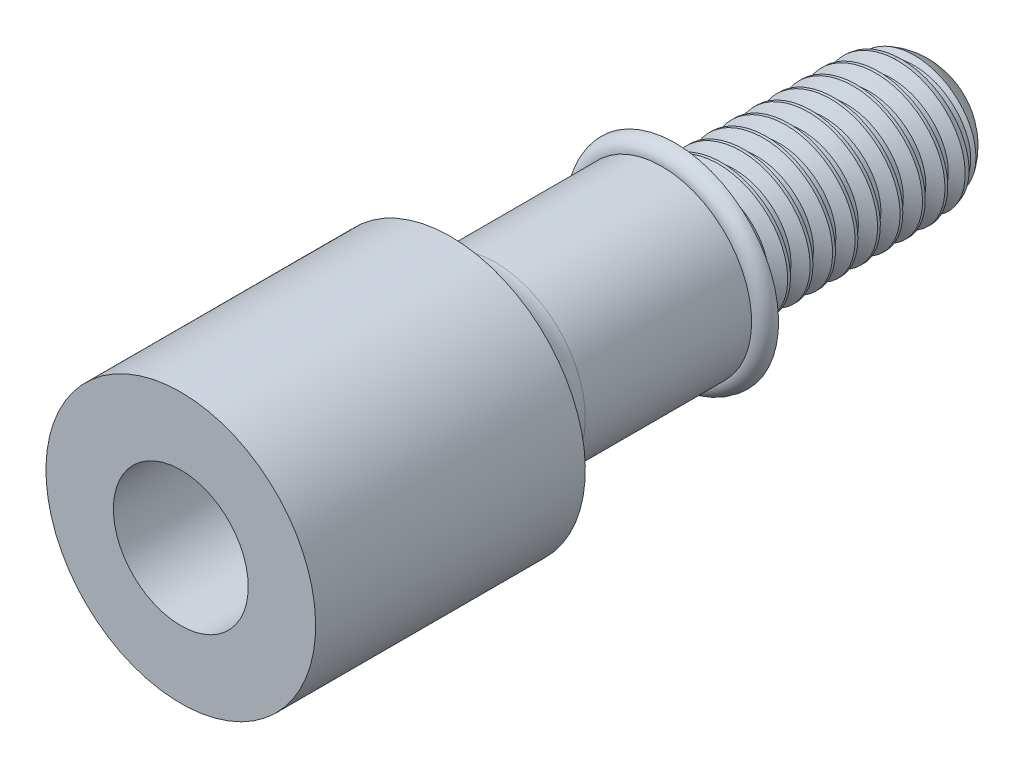
SolidWorks part; units mm, degrees
ref_plane "Front Plane" through (0, 0, 0) normal (0, 0, 1) x (1, 0, 0)
ref_plane "Top Plane" through (0, 0, 0) normal (0, 1, 0) x (1, 0, 0)
ref_plane "Right Plane" through (0, 0, 0) normal (1, 0, 0) x (0, 0, -1)
sketch "Sketch1" plane through (0, 0, 0) normal (1, 0, 0) x (0, 0, -1)
  line L0 (0, 0) -> (-11, 0)
  line L1 (-11, 0) -> (-11, 3)
  line L2 (-11, 3) -> (-5, 3)
  line L3 (-4, 2) -> (-0.3, 2)
  line L4 (0, 2.3) -> (0, 0)
  arc A0 (-5, 3) -> (-4, 2) centre (-4, 3) ccw
  arc A1 (-0.3, 2) -> (0, 2.3) centre (0, 2) cw
  dimension "D1" = 3
  dimension "D2" = 6
  dimension "D3" = 11
  dimension "D4" = 2
  dimension "D5" = 2.3
revolve "Revolve1" add sketch "Sketch1" angle 360 about L0
sketch "Sketch2" plane through (0, 0, 0) normal (0, 0, -1) x (-1, 0, 0)
  circle A0 centre (0, 0) radius 1.5
  dimension "D1" = 3
extrude "Boss-Extrude1" add sketch "Sketch2" along normal blind 6
fillet "Fillet1" radius 1.3 1 edges at (0, 1.5, -6)
thread "Thread1" pitch 0.5 method cut profile "Thread Profile1" start angle 0, offset 0, length 0, pitch 0.5, diameter 3
ref_plane "Plane1" through (1.5, 0, -6) normal (0, -1, 0) x (1, 0, 0)
sketch "Thread Profile1" plane through (1.5, 0, -6) normal (0, -1, 0) x (1, 0, 0)
  line L0 (0, 0) -> (0, 0.5) construction
  line L11 (0, 0) -> (0, 0.4375)
  line L12 (0, 0.4375) -> (-0.2706, 0.2812)
  line L13 (-0.2706, 0.2812) -> (-0.2706, 0.1562)
  line L15 (-0.2706, 0.1562) -> (0, 0)
  line L17 (-0.2706, 0.2187) -> (0, 0.2187) construction
  point P2 (0, 0)
  dimension "Pitch" = 0.5
  dimension "Profile_Angle" = 60
  dimension "Profile_Land" = 0.125
  dimension "Profile_Height" = 0.2706
sketch "Sketch6" plane through (0, 0, 11) normal (0, 0, 1) x (1, 0, 0)
  circle A0 centre (0, 0) radius 1.5
  dimension "D1" = 3
extrude "Cut-Extrude1" cut sketch "Sketch6" against normal blind 5
sketch "Sketch7" plane through (0, 0, 0) normal (1, 0, 0) x (0, 0, -1)
  line L2 (-11, 3) -> (-11, -3) construction
  circle A0 centre (-8, 0) radius 1
  dimension "D1" = 2
  dimension "D2" = 3
extrude "Cut-Extrude2" cut sketch "Sketch7" against normal through all
